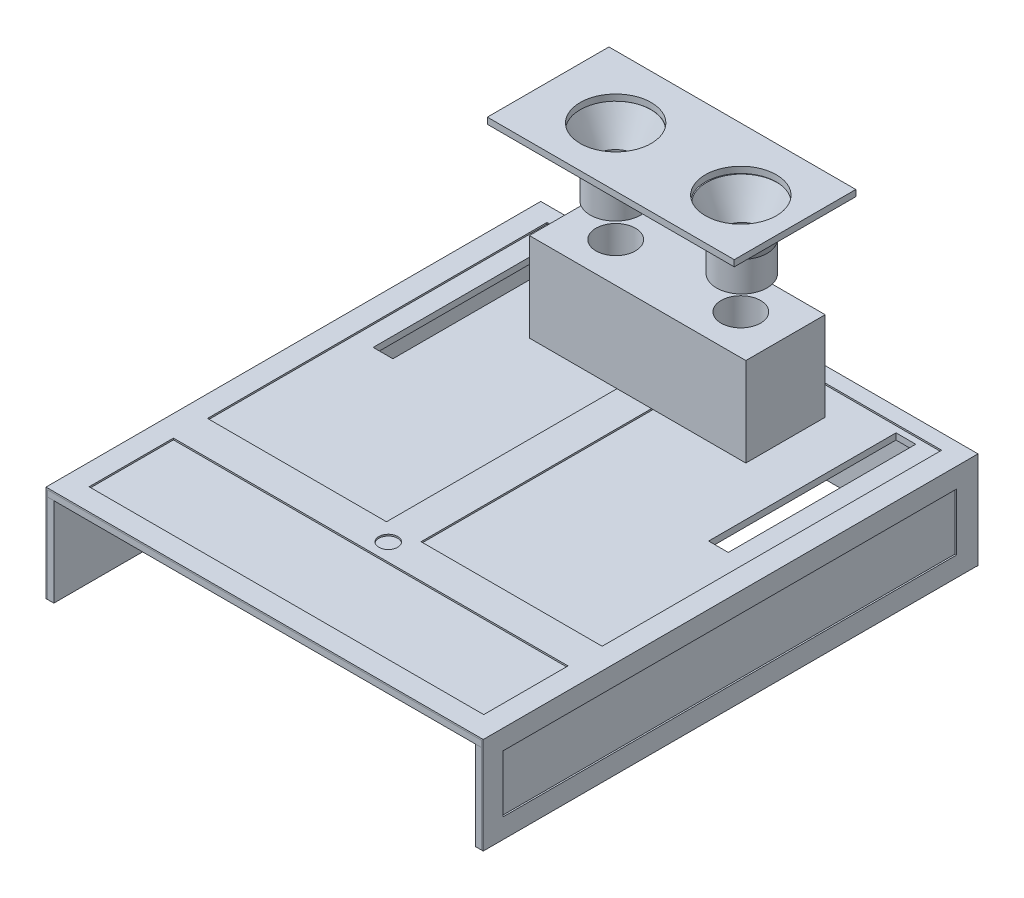
SolidWorks part; units mm, degrees
ref_plane "Front Plane" through (0, 0, 0) normal (0, 0, 1) x (1, 0, 0)
ref_plane "Top Plane" through (0, 0, 0) normal (0, 1, 0) x (1, 0, 0)
ref_plane "Right Plane" through (0, 0, 0) normal (1, 0, 0) x (0, 0, -1)
sketch "Sketch2" plane through (0, 0, 0) normal (0, 1, 0) x (1, 0, 0)
  line L7 (-162.2662, -88.2141) -> (57.7338, -88.2141)
  line L8 (27.7338, 151.7859) -> (37.7338, 151.7859)
  line L9 (57.7338, -88.2141) -> (57.7338, -68.2141)
  line L10 (57.7338, -68.2141) -> (54.5588, -68.2141)
  line L11 (54.5588, -68.2141) -> (54.5588, -48.2141)
  line L12 (54.5588, -48.2141) -> (57.7338, -48.2141)
  line L13 (-162.2662, -88.2141) -> (-162.2662, -68.2141)
  line L14 (-162.2662, -68.2141) -> (-159.0912, -68.2141)
  line L15 (-159.0912, -68.2141) -> (-159.0912, -48.2141)
  line L16 (-159.0912, -48.2141) -> (-162.2662, -48.2141)
  line L17 (-162.2662, -48.2141) -> (-162.2662, -28.2141)
  line L18 (-162.2662, -28.2141) -> (-159.0912, -28.2141)
  line L19 (-159.0912, -28.2141) -> (-159.0912, -8.2141)
  line L20 (-159.0912, -8.2141) -> (-162.2662, -8.2141)
  line L21 (57.7338, -28.2141) -> (54.5588, -28.2141)
  line L22 (54.5588, -28.2141) -> (54.5588, -8.2141)
  line L23 (54.5588, -8.2141) -> (57.7338, -8.2141)
  line L24 (57.7338, -48.2141) -> (57.7338, -28.2141)
  line L25 (-162.2662, -8.2141) -> (-162.2662, 11.7859)
  line L26 (-162.2662, 11.7859) -> (-159.0912, 11.7859)
  line L27 (-159.0912, 11.7859) -> (-159.0912, 31.7859)
  line L28 (-159.0912, 31.7859) -> (-162.2662, 31.7859)
  line L29 (57.7338, 11.7859) -> (54.5588, 11.7859)
  line L30 (54.5588, 11.7859) -> (54.5588, 31.7859)
  line L31 (54.5588, 31.7859) -> (57.7338, 31.7859)
  line L32 (57.7338, -8.2141) -> (57.7338, 11.7859)
  line L33 (-162.2662, 31.7859) -> (-162.2662, 51.7859)
  line L34 (-162.2662, 51.7859) -> (-159.0912, 51.7859)
  line L35 (-159.0912, 51.7859) -> (-159.0912, 71.7859)
  line L36 (-159.0912, 71.7859) -> (-162.2662, 71.7859)
  line L37 (57.7338, 51.7859) -> (54.5588, 51.7859)
  line L38 (54.5588, 51.7859) -> (54.5588, 71.7859)
  line L39 (54.5588, 71.7859) -> (57.7338, 71.7859)
  line L40 (57.7338, 31.7859) -> (57.7338, 51.7859)
  line L45 (27.7338, 151.7859) -> (27.7338, 56.7859)
  line L46 (27.7338, 56.7859) -> (37.7338, 56.7859)
  line L47 (37.7338, 151.7859) -> (37.7338, 56.7859)
  line L48 (-142.2662, 151.7859) -> (-132.2662, 151.7859)
  line L49 (-142.2662, 151.7859) -> (-142.2662, 56.7859)
  line L50 (-142.2662, 56.7859) -> (-132.2662, 56.7859)
  line L51 (-132.2662, 151.7859) -> (-132.2662, 56.7859)
  line L52 (-162.2662, 71.7859) -> (-162.2662, 91.7859)
  line L53 (-162.2662, 91.7859) -> (-159.0912, 91.7859)
  line L54 (-159.0912, 91.7859) -> (-159.0912, 111.7859)
  line L55 (-159.0912, 111.7859) -> (-162.2662, 111.7859)
  line L56 (57.7338, 91.7859) -> (54.5588, 91.7859)
  line L57 (54.5588, 91.7859) -> (54.5588, 111.7859)
  line L58 (54.5588, 111.7859) -> (57.7338, 111.7859)
  line L59 (57.7338, 71.7859) -> (57.7338, 91.7859)
  line L63 (-162.2662, 111.7859) -> (-162.2662, 131.7859)
  line L64 (-162.2662, 131.7859) -> (-159.0912, 131.7859)
  line L65 (-159.0912, 131.7859) -> (-159.0912, 151.7859)
  line L66 (-159.0912, 151.7859) -> (-162.2662, 151.7859)
  line L67 (57.7338, 131.7859) -> (54.5588, 131.7859)
  line L68 (54.5588, 131.7859) -> (54.5588, 151.7859)
  line L69 (54.5588, 151.7859) -> (57.7338, 151.7859)
  line L70 (57.7338, 111.7859) -> (57.7338, 131.7859)
  line L71 (57.7338, 151.7859) -> (57.7338, 161.7859)
  line L72 (57.7338, 161.7859) -> (-162.2662, 161.7859)
  line L73 (-162.2662, 161.7859) -> (-162.2662, 151.7859)
  dimension "D1" = 3.175
  dimension "D2" = 20
  dimension "D3" = 20
  dimension "D4" = 3.175
  dimension "D6" = 220
  dimension "D8" = 10
  dimension "D9" = 10
  dimension "D10" = 20
  dimension "D11" = 20
  dimension "D13" = 95
  dimension "D7" = 10
  dimension "D12" = 10
  dimension "D5" = 6
extrude "Boss-Extrude1" add sketch "Sketch2" along normal blind 3.175
sketch "Sketch3" plane through (-159.0912, 0, 0) normal (-1, 0, 0) x (0, 0, 1)
  line L0 (68.2141, 3.175) -> (68.2141, 0)
  line L1 (68.2141, 0) -> (88.2141, 0)
  line L2 (88.2141, 0) -> (88.2141, -45)
  line L3 (68.2141, 3.175) -> (48.2141, 3.175)
  line L4 (48.2141, 3.175) -> (48.2141, 0)
  line L5 (48.2141, 0) -> (28.2141, 0)
  line L6 (28.2141, 0) -> (28.2141, 3.175)
  line L7 (28.2141, 3.175) -> (8.2141, 3.175)
  line L8 (8.2141, 3.175) -> (8.2141, 0)
  line L9 (8.2141, 0) -> (-11.7859, 0)
  line L10 (-11.7859, 0) -> (-11.7859, 3.175)
  line L11 (-91.7859, 0) -> (-91.7859, 3.175)
  line L12 (-11.7859, 3.175) -> (-31.7859, 3.175)
  line L13 (-31.7859, 3.175) -> (-31.7859, 0)
  line L14 (-31.7859, 0) -> (-51.7859, 0)
  line L15 (-51.7859, 0) -> (-51.7859, 3.175)
  line L16 (-51.7859, 3.175) -> (-71.7859, 3.175)
  line L17 (-71.7859, 3.175) -> (-71.7859, 0)
  line L18 (-71.7859, 0) -> (-91.7859, 0)
  line L21 (-91.7859, 3.175) -> (-111.7859, 3.175)
  line L22 (-111.7859, 3.175) -> (-111.7859, 0)
  line L25 (-111.7859, 0) -> (-131.7859, 0)
  line L26 (-151.7859, 0) -> (-131.7859, 0) construction
  line L27 (-131.7859, 3.175) -> (-131.7859, 0) construction
  line L28 (-131.7859, 0) -> (-131.7859, 3.175)
  line L29 (-131.7859, 3.175) -> (-151.7859, 3.175)
  line L30 (-151.7859, 3.175) -> (-151.7859, 0)
  line L31 (-151.7859, 3.175) -> (-151.7859, 0) construction
  line L32 (-151.7859, 0) -> (-161.732, 0)
  line L33 (-161.732, 0) -> (-161.732, -45)
  line L34 (-161.732, -45) -> (88.2141, -45)
extrude "Boss-Extrude2" add sketch "Sketch3" along normal blind 3.175 separate body
sketch "Sketch6" plane through (0, 3.175, 0) normal (0, 1, 0) x (1, 0, 0)
  line L21 (57.7338, 161.7859) -> (57.7338, -88.2141)
  line L23 (57.7338, -88.2141) -> (-162.2662, -88.2141)
  line L25 (-162.2662, -88.2141) -> (-162.2662, 161.7859)
  line L27 (-162.2662, 161.7859) -> (57.7338, 161.7859)
  line L28 (57.7338, 111.7859) -> (57.7338, 131.7859) construction
  line L29 (57.7338, 161.7859) -> (-162.2662, 161.7859) construction
  line L30 (-152.2662, -77.1624) -> (47.7338, -77.1624)
  line L36 (-162.2662, -88.2141) -> (57.7338, -88.2141) construction
  line L37 (-61.5425, 154.9088) -> (-152.2662, 154.9088)
  line L38 (-162.2662, 51.7859) -> (-162.2662, 31.7859) construction
  line L39 (-152.2662, -77.1624) -> (-152.2662, -34.4256)
  line L40 (-152.2662, -34.4256) -> (47.7338, -34.4256)
  line L41 (47.7338, -77.1624) -> (47.7338, -34.4256)
  line L43 (-152.2662, 154.9088) -> (-152.2662, -17.1634)
  line L44 (-152.2662, -17.1634) -> (-61.5425, -17.1634)
  line L46 (-44.0444, -17.1634) -> (47.7338, -17.1634)
  line L47 (-44.0444, -17.1634) -> (-44.0444, 154.9088)
  line L48 (-44.0444, 154.9088) -> (47.7338, 154.9088)
  line L49 (47.7338, -17.1634) -> (47.7338, 154.9088)
  line L50 (-61.5425, 154.9088) -> (-61.5425, -17.1634)
  circle A0 centre (-52.2662, -25.5384) radius 4.757
  point P21 (-51.5647, -33.7771)
  point P26 (-52.2662, -36.6415)
  point P27 (-52.2662, -25.5384)
extrude "Boss-Extrude5" add sketch "Sketch6" along normal blind 0.8 separate body
sketch "Sketch9" plane through (-162.2662, 0, 0) normal (-1, 0, 0) x (0, 0, 1)
  line L0 (-161.732, 3.975) -> (-161.732, -45)
  line L1 (-161.732, -45) -> (88.2141, -45)
  line L2 (88.2141, -45) -> (88.2141, 3.975)
  line L3 (88.2141, 3.975) -> (-161.732, 3.975)
  line L4 (78.2141, -6.025) -> (-151.732, -6.025)
  line L5 (-151.732, -6.025) -> (-151.732, -35)
  line L6 (-151.732, -35) -> (78.2141, -35)
  line L7 (78.2141, -35) -> (78.2141, -6.025)
  line L8 (-161.732, 0) -> (-161.732, -45) construction
  point P3 (0, 0)
  point P6 (0, 0)
  point P12 (0, 0)
  point P13 (0, 0)
  point P14 (0, 0)
  point P15 (0, 0)
  point P16 (0, 0)
  point P17 (0, 0)
  point P19 (0, 0)
extrude "Boss-Extrude7" add sketch "Sketch9" along normal blind 0.8
ref_plane "Plane3" through (-52.2662, 0, 0) normal (-1, 0, 0) x (0, 0, 1)
sketch "Sketch10" plane through (0, 3.975, 0) normal (0, 1, 0) x (1, 0, 0)
  line L0 (3.7439, 139.8898) -> (-105.9534, 139.8898)
  line L1 (3.7439, 139.8898) -> (3.7439, 99.6617)
  line L2 (-105.9534, 139.8898) -> (-105.9534, 99.6617)
  line L3 (3.7439, 99.6617) -> (-105.9534, 99.6617)
  point P4 (-51.1048, 119.7757)
  point P7 (-84.1192, 119.7757)
  point P12 (-19.3564, 119.7757)
  point P13 (-18.2398, 119.7757)
extrude "Boss-Extrude8" add sketch "Sketch10" along normal blind 45 separate body
sketch "Sketch11" plane through (0, 48.975, 0) normal (0, 1, 0) x (1, 0, 0)
  circle A1 centre (-82.3327, 119.7757) radius 10
  circle A2 centre (-18.9098, 119.7757) radius 10
  point P2 (-51.1048, 119.7757)
  point P5 (-82.3327, 119.7757)
  point P8 (-18.9098, 119.7757)
extrude "Cut-Extrude1" cut sketch "Sketch11" against normal blind 30
sketch "Sketch12" plane through (0, 3.975, 0) normal (0, 1, 0) x (1, 0, 0)
  circle A0 centre (-113.3178, 147.3993) radius 3.4149
  point P2 (-113.3178, 147.3993)
extrude "Boss-Extrude9" add sketch "Sketch12" along normal blind 93 separate body
sketch "Sketch13" plane through (0, 96.975, 0) normal (0, 1, 0) x (1, 0, 0)
  line L0 (-117.4222, 151.4397) -> (7.7034, 151.4397)
  line L1 (-117.4222, 151.4397) -> (-117.4222, 89.8269)
  line L2 (7.7034, 151.4397) -> (7.7034, 89.8269)
  line L3 (-117.4222, 89.8269) -> (7.7034, 89.8269)
  circle A0 centre (-82.3327, 119.7757) radius 18
  circle A2 centre (-18.9098, 119.7757) radius 18
  point P4 (0, 0)
  point P5 (0, 0)
  point P6 (-51.1048, 119.7757)
  point P13 (-18.9098, 119.7757)
extrude "Boss-Extrude10" add sketch "Sketch13" along normal blind 3.175
ref_plane "Plane1" through (-82.4222, 0, 0) normal (1, 0, 0) x (0, 0, -1)
sketch "Sketch14" plane through (-82.4222, 0, 0) normal (1, 0, 0) x (0, 0, -1)
  line L0 (101.834, 96.975) -> (109.6255, 81.2515)
  line L1 (89.8269, 96.975) -> (151.4397, 96.975) construction
  line L2 (109.6255, 81.2515) -> (106.9626, 81.2515)
  line L3 (106.9626, 81.2515) -> (99.3429, 96.975)
  line L4 (99.3429, 96.975) -> (101.834, 96.975)
  line L5 (119.7757, 48.975) -> (119.7757, 121.3419) construction
  line L6 (99.6617, 48.975) -> (139.8898, 48.975) construction
  point P2 (108.9502, 80.404)
  point P9 (119.7757, 48.975)
  point P12 (101.2551, 80.3797)
  point P13 (104.3019, 80.4844)
  point P14 (106.0798, 80.271)
  point P15 (103.1576, 80.9023)
  point P16 (105.7314, 80.9421)
  point P17 (100.2571, 96.975)
  point P18 (0, 0)
  point P19 (101.834, 96.975)
  point P20 (99.3429, 96.975)
  point P21 (106.9626, 81.2515)
revolve "Revolve1" add sketch "Sketch14" angle 360 about L5
ref_plane "Plane2" through (-50.4222, 0, 0) normal (-1, 0, 0) x (0, 0, 1)
sketch "Sketch16" plane through (0, 81.2515, 0) normal (0, -1, 0) x (1, 0, 0)
  circle A2 centre (-82.4222, -119.7757) radius 10.2644
  circle A3 centre (-82.4222, -119.7757) radius 12.8132
extrude "Boss-Extrude11" add sketch "Sketch16" along normal blind 15.175
mirror "Mirror2" about plane through (-50.4222, 0, 0) normal (-1, 0, 0) of "Boss-Extrude11", "Revolve1"
mirror "Mirror4" about plane through (-52.2662, 0, 0) normal (-1, 0, 0) of bodies 103
mirror "Mirror5" about plane through (-52.2662, 0, 0) normal (-1, 0, 0) of "Boss-Extrude7"
sketch "Sketch17" plane through (0, 0, -161.732) normal (0, 0, -1) x (-1, 0, 0)
  line L0 (-58.5338, 3.975) -> (163.0662, 3.975)
  line L1 (-58.5338, 3.975) -> (-58.5338, -45.1595)
  line L2 (163.0662, 3.975) -> (163.0662, -45.1595)
  line L3 (-58.5338, -45.1595) -> (163.0662, -45.1595)
extrude "Boss-Extrude12" add sketch "Sketch17" along normal blind 0.8
equation "\"hardboard_width\"= 3.175"
equation "\"D1@Boss-Extrude1\"=\"hardboard_width\""
equation "\"D1@Sketch2\"=\"hardboard_width\""
equation "\"D4@Sketch2\"=\"hardboard_width\""
equation "\"D1@Boss-Extrude2\"=\"hardboard_width\""
equation "\"steel_24g_thickness\"= 0.8"
equation "\"D1@Boss-Extrude5\"=\"steel_24g_thickness\""
equation "\"D1@Boss-Extrude7\"=\"steel_24g_thickness\""
equation "\"D1@Boss-Extrude10\"=\"hardboard_width\""
equation "\"D1@Boss-Extrude12\"=\"steel_24g_thickness\""
